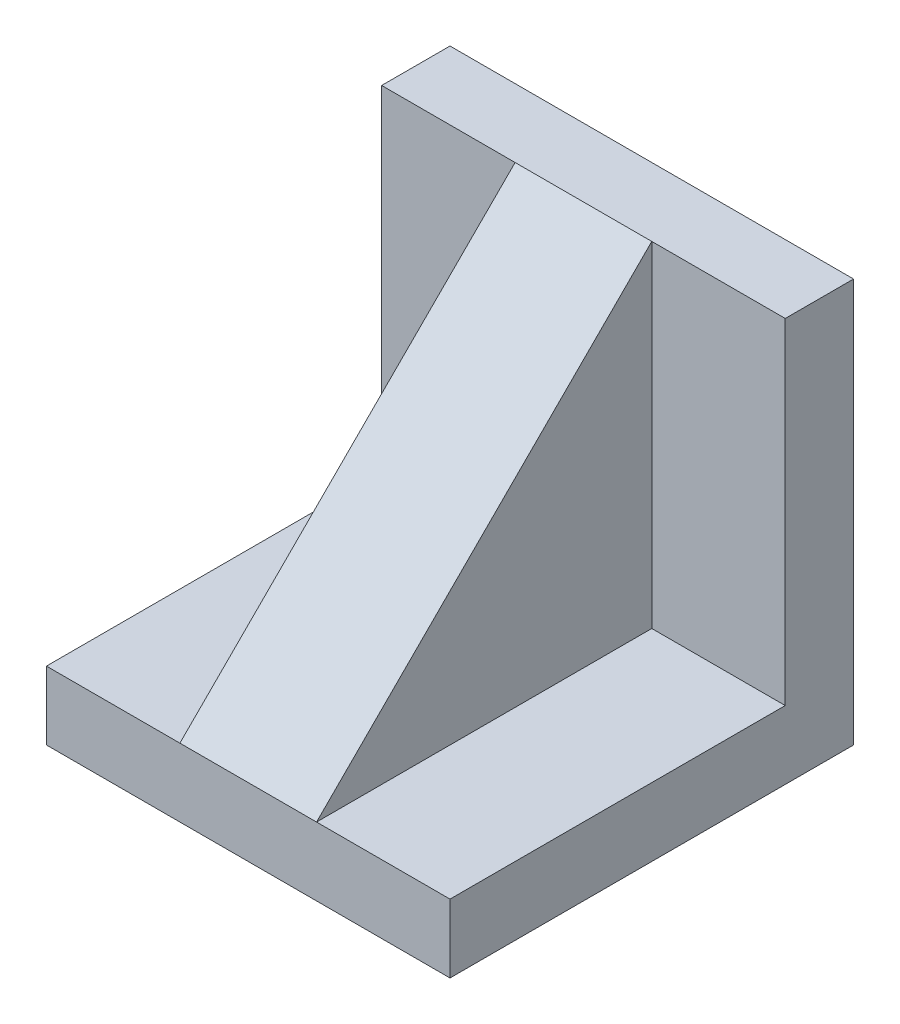
SolidWorks part; units mm, degrees
ref_plane "Front Plane" through (0, 0, 0) normal (1, 0, 0) x (0, 1, 0)
ref_plane "Top Plane" through (0, 0, 0) normal (0, 0, 1) x (0, 1, 0)
ref_plane "Right Plane" through (0, 0, 0) normal (0, 1, 0) x (-1, 0, 0)
sketch "Sketch1" plane through (0, 0, 0) normal (1, 0, 0) x (0, 1, 0)
  line L0 (0, 0) -> (0, 150)
  line L1 (0, 150) -> (25.4, 150)
  line L2 (25.4, 150) -> (25.4, 25.4)
  line L3 (25.4, 25.4) -> (150, 25.4)
  line L4 (150, 25.4) -> (150, 0)
  line L5 (150, 0) -> (0, 0)
  dimension "D1" = 25.4
  dimension "D2" = 150
  dimension "D3" = 150
  dimension "D4" = 25.4
extrude "Boss-Extrude1" add sketch "Sketch1" along normal blind 75 and the other way blind 75 contours L2 L3 L4 L5 L0 L1
sketch "Sketch3" plane through (0, 0, 0) normal (1, 0, 0) x (0, 1, 0)
  line L0 (0, 150) -> (25.4, 150)
  line L1 (25.4, 150) -> (150, 25.4)
  line L2 (150, 25.4) -> (150, 0)
  line L3 (150, 0) -> (0, 0)
  line L4 (0, 0) -> (0, 150)
  line L6 (150, 25.4) -> (150, 0) construction
extrude "Boss-Extrude2" add sketch "Sketch3" along normal blind 25.4 and the other way blind 25.4
